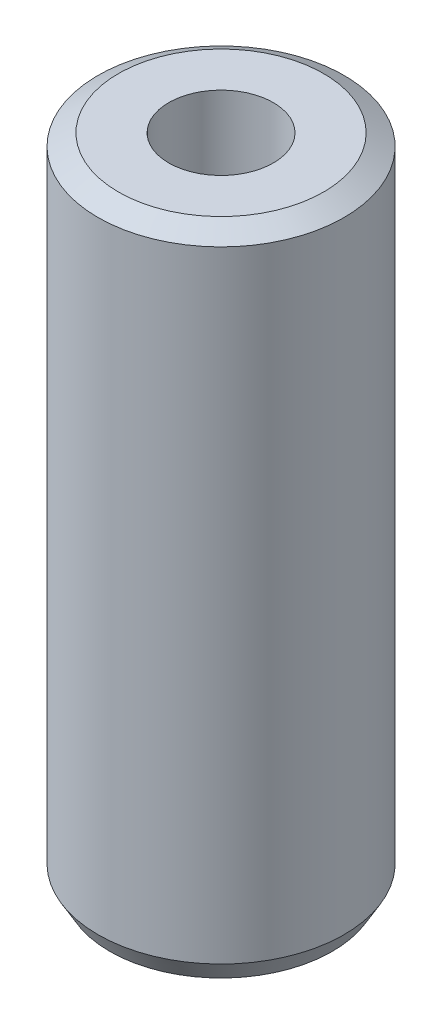
SolidWorks part; units mm, degrees
ref_plane "Front Plane" through (0, 0, 0) normal (0, 0, 1) x (1, 0, 0)
ref_plane "Top Plane" through (0, 0, 0) normal (0, 1, 0) x (1, 0, 0)
ref_plane "Right Plane" through (0, 0, 0) normal (1, 0, 0) x (0, 0, -1)
sketch "Sketch1" plane through (0, 0, 0) normal (0, 1, 0) x (1, 0, 0)
  circle A0 centre (0, 0) radius 32.5
  dimension "SHAFT_OD" = 65
extrude "Boss-Extrude1" add sketch "Sketch1" along normal blind 172.5202
sketch "Sketch2" plane through (0, 0, 0) normal (0, 1, 0) x (1, 0, 0)
  circle A0 centre (0, 0) radius 13.8139
  dimension "BORE_D" = 27.6279
extrude "Cut-Extrude1" cut sketch "Sketch2" along normal through all
chamfer "Chamfer1" distance 3.12 angle 60 2 edges at (0, 172.5202, 32.5) (0, 0, 32.5) first distance on face at (0, 172.5202, 32.5) first distance on face at (0, 0, 13.8139)
